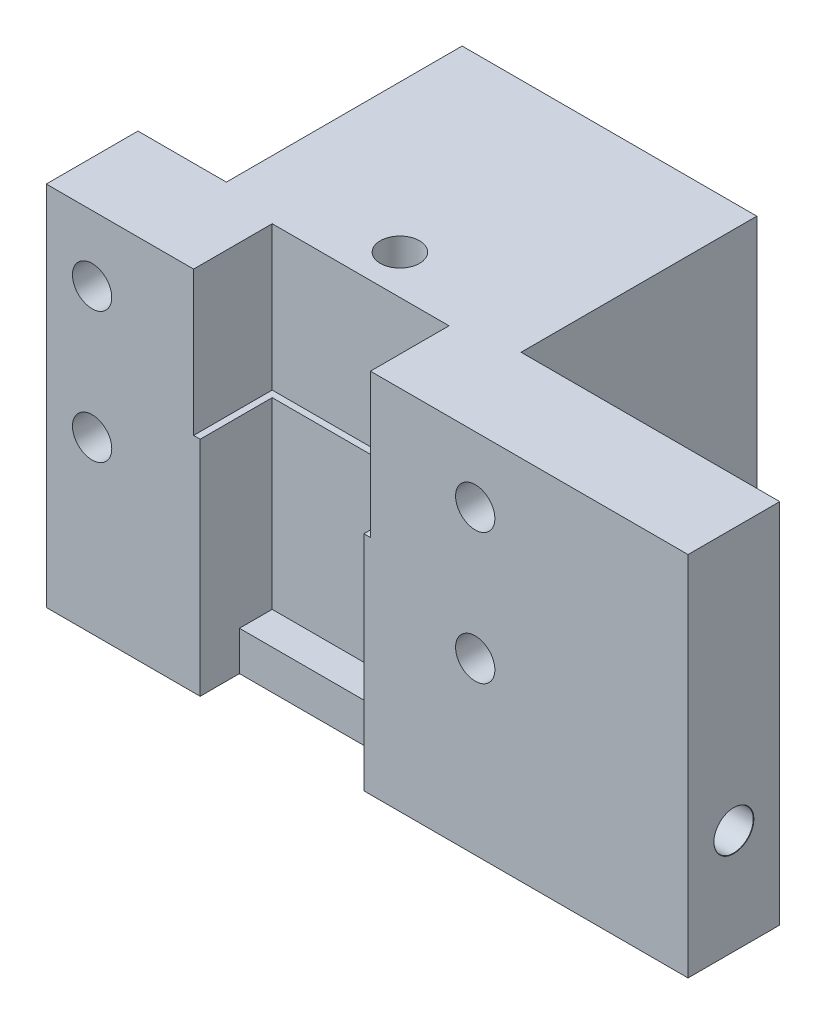
SolidWorks part; units mm, degrees
ref_plane "Front Plane" through (0, 0, 0) normal (0, 0, 1) x (1, 0, 0)
ref_plane "Top Plane" through (0, 0, 0) normal (0, 1, 0) x (1, 0, 0)
ref_plane "Right Plane" through (0, 0, 0) normal (1, 0, 0) x (0, 0, -1)
sketch "Sketch1" plane through (0, 0, 0) normal (0, 1, 0) x (1, 0, 0)
  line L1 (-10.5256, 12.3096) -> (38.4744, 12.3096)
  line L2 (-10.5256, 12.3096) -> (-10.5256, -12.6904)
  line L3 (-10.5256, -12.6904) -> (38.4744, -12.6904)
  line L4 (38.4744, 12.3096) -> (38.4744, -12.6904)
  dimension "D1" = 25
  dimension "D2" = 49
extrude "Boss-Extrude1" add sketch "Sketch1" along normal blind 28
sketch "Sketch2" plane through (0, 28, 0) normal (0, 1, 0) x (1, 0, 0)
  line L0 (-10.5256, -12.6904) -> (38.4744, -12.6904) construction
  line L1 (1.2244, -12.6904) -> (13.7244, -12.6904)
  line L2 (1.2244, -12.6904) -> (1.2244, -7.1904)
  line L3 (1.2244, -7.1904) -> (13.7244, -7.1904)
  line L4 (13.7244, -12.6904) -> (13.7244, -7.1904)
  line L5 (-10.5256, 12.3096) -> (-10.5256, -12.6904) construction
  dimension "D1" = 11.75
  dimension "D2" = 12.5
  dimension "D3" = 5.5
extrude "Cut-Extrude1" cut sketch "Sketch2" against normal blind 25
hole_wizard "Ø3.0mm Dowel Hole1" positions "Sketch3" profile "Sketch4" hole size "Ø3.0" standard "ANSI Metric"
sketch "Sketch3" plane through (0, 0, -12.3096) normal (0, 0, -1) x (-1, 0, 0)
  line L0 (-38.4744, 28) -> (-38.4744, 0) construction
  line L3 (-38.4744, 0) -> (10.5256, 0) construction
  point P0 (-7.4744, 16)
  dimension "D1" = 31
  dimension "D2" = 16
sketch "Sketch4" plane through (7.4744, 16, -12.3096) normal (1, 0, 0) x (0, 1, 0)
  line L0 (0, 0) -> (0, 12)
  line L1 (0, 12) -> (1.5, 11.0987)
  line L2 (1.5, 11.0987) -> (1.5, 0.025)
  line L3 (1.5, 0.025) -> (1.525, 0)
  line L5 (1.525, 0) -> (0, 0)
  line L6 (-1.5, 0.025) -> (-1.525, 0) construction
  line L10 (0, 12) -> (-1.5, 11.0987) construction
  line L11 (0, -6.35) -> (0, 107.95) construction
  dimension "Hole Dia." = 3
  dimension "Hole Depth" = 12
  dimension "Near C'Sink Dia." = 3.05
  dimension "Near C'Sink Angle" = 90
  dimension "Drill Angle" = 118
hole_wizard "Ø3.0mm Dowel Hole2" positions "Sketch7" profile "Sketch8" hole size "Ø3.0" standard "ANSI Metric" end condition up to next
sketch "Sketch7" plane through (38.4744, 0, 0) normal (1, 0, 0) x (0, 0, -1)
  line L0 (-12.6904, 0) -> (12.3096, 0) construction
  line L1 (12.3096, 28) -> (12.3096, 0) construction
  point P0 (-9.1904, 8)
  dimension "D1" = 8
  dimension "D2" = 21.5
sketch "Sketch8" plane through (38.4744, 8, 9.1904) normal (0, 1, 0) x (0, 0, -1)
  line L0 (0, 0) -> (0, 24.75)
  line L1 (0, 24.75) -> (1.5, 24.75)
  line L2 (1.5, 24.75) -> (1.5, 0.025)
  line L3 (1.5, 0.025) -> (1.525, 0)
  line L5 (1.525, 0) -> (0, 0)
  line L6 (-1.5, 0.025) -> (-1.525, 0) construction
  line L11 (0, -6.35) -> (0, 107.95) construction
  dimension "Thru Hole Dia." = 3
  dimension "Thru Hole Depth" = 24.75
  dimension "Near C'Sink Dia." = 3.05
  dimension "Near C'Sink Angle" = 90
hole_wizard "Ø3.0mm Dowel Hole3" positions "Sketch9" profile "Sketch10" hole size "Ø3.0" standard "ANSI Metric" end condition through all
sketch "Sketch9" plane through (0, 0, 0) normal (0, -1, 0) x (-1, 0, 0)
  line L1 (-38.4744, 12.3096) -> (10.5256, 12.3096) construction
  line L3 (-38.4744, -12.6904) -> (-38.4744, 12.3096) construction
  point P0 (-7.4744, -3.6904)
  dimension "D1" = 31
  dimension "D2" = 16
sketch "Sketch10" plane through (7.4744, 0, 3.6904) normal (1, 0, 0) x (0, 0, -1)
  line L0 (0, 0) -> (0, 28)
  line L1 (0, 28) -> (1.5, 28)
  line L2 (1.5, 28) -> (1.5, 0.025)
  line L3 (1.5, 0.025) -> (1.525, 0)
  line L5 (1.525, 0) -> (0, 0)
  line L6 (-1.5, 0.025) -> (-1.525, 0) construction
  line L11 (0, -6.35) -> (0, 107.95) construction
  dimension "Thru Hole Dia." = 3
  dimension "Thru Hole Depth" = 28
  dimension "Near C'Sink Dia." = 3.05
  dimension "Near C'Sink Angle" = 90
sketch "Sketch13" plane through (0, 0, 12.6904) normal (0, 0, 1) x (1, 0, 0)
  line L0 (-10.5256, 28) -> (1.2244, 28) construction
  line L1 (13.7244, 28) -> (38.4744, 28) construction
  line L6 (-10.5256, 28) -> (-10.5256, 0) construction
  line L7 (13.7244, 3) -> (13.7244, 28) construction
  line L8 (13.7244, 3) -> (13.7244, 28) construction
  circle A0 centre (-7.0256, 23) radius 1.5
  circle A3 centre (-7.0256, 13) radius 1.5
  circle A4 centre (22.2244, 23) radius 1.5
  circle A5 centre (22.2244, 13) radius 1.5
  dimension "D1" = 5
  dimension "D2" = 5
  dimension "D3" = 10
  dimension "D4" = 3.5
  dimension "D5" = 8.5
  dimension "D6" = 8.5
  dimension "D8" = 10
extrude "Cut-Extrude2" cut sketch "Sketch13" against normal blind 12
sketch "Sketch14" plane through (0, 28, 0) normal (0, 1, 0) x (1, 0, 0)
  line L0 (-10.5256, -12.6904) -> (1.2244, -12.6904) construction
  line L1 (-10.5256, 12.3096) -> (-3.7756, 12.3096)
  line L2 (-10.5256, 12.3096) -> (-10.5256, -5.6904)
  line L3 (-10.5256, -5.6904) -> (-3.7756, -5.6904)
  line L4 (-3.7756, 12.3096) -> (-3.7756, -5.6904)
  line L5 (1.2244, -7.1904) -> (1.2244, -12.6904) construction
  line L6 (13.7244, -12.6904) -> (38.4744, -12.6904) construction
  line L7 (18.7244, 12.3096) -> (38.4744, 12.3096)
  line L8 (18.7244, 12.3096) -> (18.7244, -5.6904)
  line L9 (18.7244, -5.6904) -> (38.4744, -5.6904)
  line L10 (38.4744, 12.3096) -> (38.4744, -5.6904)
  line L11 (13.7244, -12.6904) -> (13.7244, -7.1904) construction
  dimension "D1" = 7
  dimension "D2" = 5
  dimension "D3" = 7
  dimension "D4" = 5
extrude "Cut-Extrude3" cut sketch "Sketch14" against normal blind 28
sketch "Sketch15" plane through (0, 3, 0) normal (0, 1, 0) x (1, 0, 0)
  line L0 (13.7244, -12.6904) -> (13.7244, -7.1904) construction
  line L1 (1.2244, -12.6904) -> (13.7244, -12.6904)
  line L2 (1.2244, -12.6904) -> (1.2244, -9.6904)
  line L3 (1.2244, -9.6904) -> (13.7244, -9.6904)
  line L4 (13.7244, -12.6904) -> (13.7244, -9.6904)
  dimension "D1" = 3
extrude "Cut-Extrude4" cut sketch "Sketch15" against normal blind 10
sketch "Sketch16" plane through (0, 28, 0) normal (0, 1, 0) x (1, 0, 0)
  line L3 (13.7244, -12.6904) -> (13.7244, -7.1904) construction
  line L4 (13.7244, -7.1904) -> (1.2244, -7.1904) construction
  line L5 (1.2244, -7.1904) -> (1.2244, -12.6904) construction
  line L6 (14.2244, -12.6904) -> (14.2244, -6.6904)
  line L7 (14.2244, -6.6904) -> (0.7244, -6.6904)
  line L8 (0.7244, -6.6904) -> (0.7244, -12.6904)
  line L9 (14.2244, -12.6904) -> (14.2244, -6.6904)
  line L10 (14.2244, -6.6904) -> (0.7244, -6.6904)
  line L11 (0.7244, -6.6904) -> (0.7244, -12.6904)
  line L12 (13.7244, -12.6904) -> (13.7244, -7.1904)
  line L13 (13.7244, -7.1904) -> (1.2244, -7.1904)
  line L14 (1.2244, -7.1904) -> (1.2244, -12.6904)
  line L15 (0.7244, -12.6904) -> (1.2244, -12.6904)
  line L16 (13.7244, -12.6904) -> (14.2244, -12.6904)
  dimension "D1" = 0.5
extrude "Cut-Extrude5" cut sketch "Sketch16" against normal blind 11
